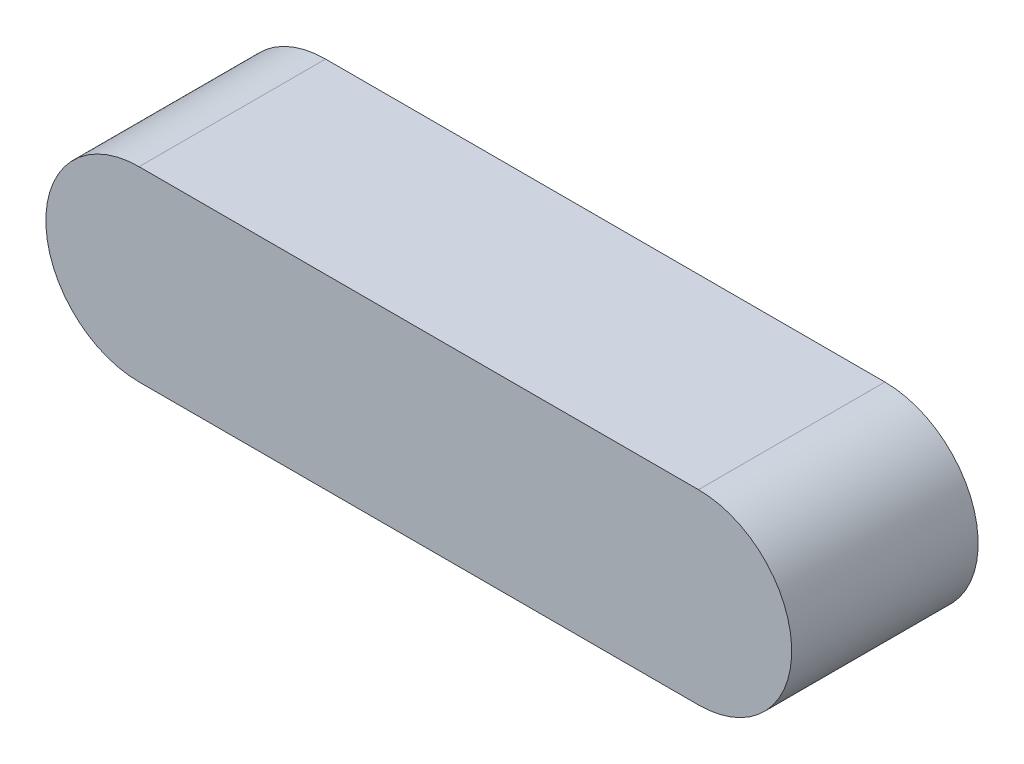
SolidWorks part; units mm, degrees
ref_plane "Front Plane" through (0, 0, 0) normal (0, 0, 1) x (1, 0, 0)
ref_plane "Top Plane" through (0, 0, 0) normal (0, 1, 0) x (1, 0, 0)
ref_plane "Right Plane" through (0, 0, 0) normal (1, 0, 0) x (0, 0, -1)
sketch "Sketch2" plane through (0, 0, 0) normal (0, 0, 1) x (1, 0, 0)
  line L0 (-9.525, 0) -> (9.525, 0) construction
  line L1 (-9.525, 3.175) -> (9.525, 3.175)
  line L2 (-9.525, -3.175) -> (9.525, -3.175)
  arc A0 (-9.525, 3.175) -> (-9.525, -3.175) centre (-9.525, 0) ccw
  arc A1 (9.525, -3.175) -> (9.525, 3.175) centre (9.525, 0) ccw
  point P2 (0, 0)
  dimension "D1" = 3.175
  dimension "D2" = 19.05
extrude "Boss-Extrude1" add sketch "Sketch2" along normal blind 3.175 and the other way blind 3.175
